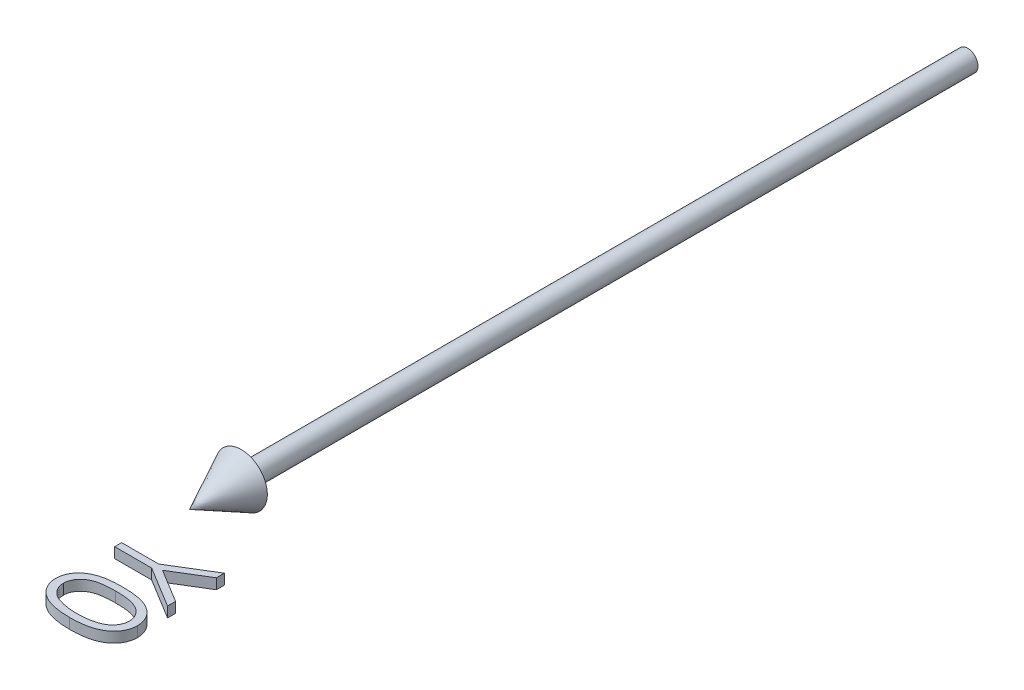
SolidWorks part; units mm, degrees
ref_plane "Front Plane" through (0, 0, 0) normal (0, 0, 1) x (1, 0, 0)
ref_plane "Top Plane" through (0, 0, 0) normal (0, 1, 0) x (1, 0, 0)
ref_plane "Right Plane" through (0, 0, 0) normal (1, 0, 0) x (0, 0, -1)
sketch "Sketch2" plane through (0, 0, 0) normal (0, 1, 0) x (1, 0, 0)
  line L0 (0, 41.95) -> (0, -114.4521) construction
  line L1 (-36.8894, 0) -> (41.4965, 0) construction
  line L2 (0, -150) -> (5, -140)
  line L3 (5, -140) -> (2, -140)
  line L4 (2, -140) -> (2, 0)
  line L5 (2, 0) -> (0, 0)
  line L6 (0, 0) -> (0, -150)
  dimension "D1" = 150
  dimension "D2" = 2
  dimension "D3" = 10
  dimension "D4" = 5
revolve "Revolve1" add sketch "Sketch2" angle 360 about L0
sketch "Sketch3" plane through (0, 0, 0) normal (0, 1, 0) x (1, 0, 0)
  line L0 (0, -157.5) -> (0, -276.9246) construction
  line L1 (-44.8388, 0) -> (53.6571, 0) construction
  text T0 "Y0\r\n" font "Century Gothic" height 15
  dimension "D1" = 157.5
extrude "Boss-Extrude1" add sketch "Sketch3" against normal blind 1 and the other way blind 1 separate body
equation "\"D1@Sketch2\"=\"frame_arrow_length\""
equation "\"D2@Sketch2\"=\"frame_arrow_odA\"/2"
equation "\"D4@Sketch2\"=\"frame_arrow_head_od\""
equation "\"D3@Sketch2\"=\"frame_arrow_head_length\""
equation "\"frame_arrow_length\"=150"
equation "\"frame_arrow_head_length\"=10"
equation "\"frame_arrow_head_od\"=5"
equation "\"frame_arrow_odA\"=4"
equation "\"D1@Sketch3\"=\"frame_arrow_length\"*1.05"
